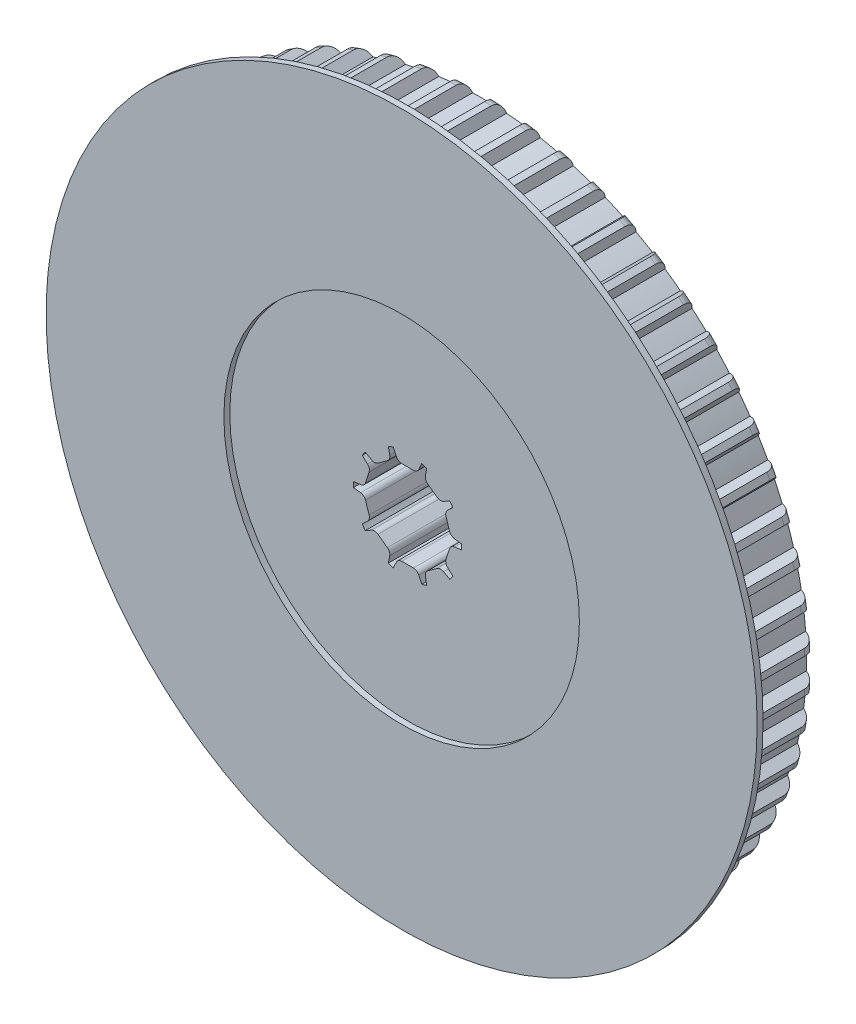
SolidWorks part; units mm, degrees
material "PMMA"
ref_plane "Ebene vorne" through (0, 0, 0) normal (0, 0, 1) x (1, 0, 0)
ref_plane "Ebene oben" through (0, 0, 0) normal (0, 1, 0) x (1, 0, 0)
ref_plane "Ebene rechts" through (0, 0, 0) normal (1, 0, 0) x (0, 0, -1)
ref_axis "Achse1" through (0, 0, 0.375) along (0, 0, -1)
sketch "Skizze1" plane through (0, 0, 0) normal (1, 0, 0) x (0, 0, -1)
  line L0 (0, 31.7827) -> (0, -32.6712) construction
  line L1 (-33.2769, 0) -> (37.2346, 0) construction
  line L2 (0, 4.57) -> (0, 28.24)
  line L3 (0, 28.24) -> (5.3, 28.24)
  line L4 (6.3, 27.24) -> (6.3, 6.1)
  line L6 (7.1, 6.1) -> (7.1, 4.57)
  line L7 (7.1, 4.57) -> (0, 4.57)
  line L8 (7.1, 6.1) -> (6.3, 6.1)
  arc A1 (5.3, 28.24) -> (6.3, 27.24) centre (5.3, 27.24) cw
  point P19 (6.3, 28.24)
  dimension "D8" = 1
  dimension "D1" = 6.3
  dimension "D2" = 56.48
  dimension "D3" = 0.8
  dimension "D5" = 6.1
  dimension "D7" = 9.14
revolve "Rotation1" add sketch "Skizze1" angle 360 about L1
sketch "Skizze2" plane through (0, 0, 0) normal (0, 0, 1) x (1, 0, 0)
  line L0 (0, 25.2337) -> (0, -18.8875) construction
  line L1 (18.5217, 0) -> (-21.6513, 0) construction
  line L2 (0.803, 27.3632) -> (1.2, 28.2145)
  line L3 (-0.803, 27.3632) -> (-1.2, 28.2145)
  circle A0 centre (0, 0) radius 28.24 construction
  circle A1 centre (0, 0) radius 27.375 construction
  circle A2 centre (0, 0) radius 28.24 construction
  arc A3 (0.803, 27.3632) -> (-0.803, 27.3632) centre (0, 0) ccw
  arc A4 (1.2, 28.2145) -> (-1.2, 28.2145) centre (0, 0) ccw
  dimension "D1" = 54.75
  dimension "D2" = 50
  dimension "D3" = 2.4
  dimension "D4" = 1.6061
extrude "Schnitt-Linear austragen1" cut sketch "Skizze2" against normal through all
pattern_circular "Kreismuster1" count 60 over 360 about axis through (0, 0, 0.375) along (0, 0, -1) of "Schnitt-Linear austragen1"
sketch "Skizze3" plane through (0, 0, 0) normal (0, 0, 1) x (1, 0, 0)
  line L0 (0, 18.7184) -> (0, -16.4301) construction
  line L1 (17.9538, 0) -> (-20.4113, 0) construction
  line L2 (0.8085, 3.57) -> (1.2, 4.4096)
  line L3 (-0.8085, 3.57) -> (-1.2, 4.4096)
  line L4 (0.8085, 3.57) -> (-0.8085, 3.57)
  line L5 (-2.5176, 4.57) -> (3.1687, 4.57) construction
  circle A0 centre (0, 0) radius 4.57 construction
  circle A2 centre (0, 0) radius 4.57 construction
  arc A3 (1.2, 4.4096) -> (-1.2, 4.4096) centre (0, 0) ccw
  dimension "D1" = 9.14
  dimension "D2" = 1
  dimension "D3" = 50
  dimension "D4" = 2.4
  dimension "D5" = 1.6169
extrude "Aufsatz-Linear austragen1" add sketch "Skizze3" against normal up to surface (7.1 mm away) up to face at (6.1, 0, -7.1)
fillet "Verrundung1" radius 0.5 2 edges at (0.8085, 3.57, -3.55) (-0.8085, 3.57, -3.55)
pattern_circular "Kreismuster2" count 10 over 360 about axis through (0, 0, 0.375) along (0, 0, -1) of "Aufsatz-Linear austragen1", "Verrundung1"
sketch "Skizze4" plane through (0, 0, 0) normal (1, 0, 0) x (0, 0, -1)
  line L0 (0, 19.3542) -> (0, -18.0091) construction
  line L1 (-12.7482, 0) -> (17.6163, 0) construction
  line L2 (0, 15) -> (-0.5, 15)
  line L3 (-0.5, 15) -> (-0.5, 30)
  line L4 (-0.5, 30) -> (0, 30)
  line L5 (0, 30) -> (0, 28.5)
  line L6 (0, 28.5) -> (0.6536, 27.8464)
  line L7 (0.8, 27.4929) -> (0.8, 26)
  line L8 (0.8, 26) -> (0, 26)
  line L9 (0, 26) -> (0, 15)
  arc A0 (0.8, 27.4929) -> (0.6536, 27.8464) centre (0.3, 27.4929) ccw
  dimension "D8" = 0.5
  dimension "D1" = 30
  dimension "D2" = 0.5
  dimension "D3" = 60
  dimension "D4" = 28.5
  dimension "D5" = 45
  dimension "D6" = 0.8
  dimension "D7" = 26
revolve "Rotation2" add sketch "Skizze4" angle 360 about L1
sketch "Skizze5" plane through (0, 0, 0) normal (1, 0, 0) x (0, 0, -1)
  line L0 (13.5237, 0) -> (-4.1574, 0) construction
  line L1 (0, -18.0539) -> (0, 17.4561) construction
  line L2 (7.1, 4.2) -> (6.3, 5)
  line L3 (6.3, 5) -> (6.3, 6.1)
  line L4 (6.3, 6.1) -> (7.1, 6.1)
  line L5 (7.1, 6.1) -> (7.1, 4.2)
  line L6 (6.3, -6.1) -> (6.3, 6.1) construction
  line L7 (7.1, -6.1) -> (7.1, 6.1) construction
  line L8 (7.1, 6.1) -> (6.3, 6.1) construction
  dimension "D1" = 135
  dimension "D2" = 5
revolve "Schnitt-Rotation1" cut sketch "Skizze5" angle 360 about L0
fillet "Verrundung2" radius 0.5 10 edges at (2.4687, 3.3979, -7.1) (0, 4.2, -7.1) (-2.4687, 3.3979, -7.1) (-3.9944, 1.2979, -7.1) (-3.9944, -1.2979, -7.1) (-2.4687, -3.3979, -7.1) (3.9944, 1.2979, -7.1) (3.9944, -1.2979, -7.1) (2.4687, -3.3979, -7.1) (0, -4.2, -7.1)
